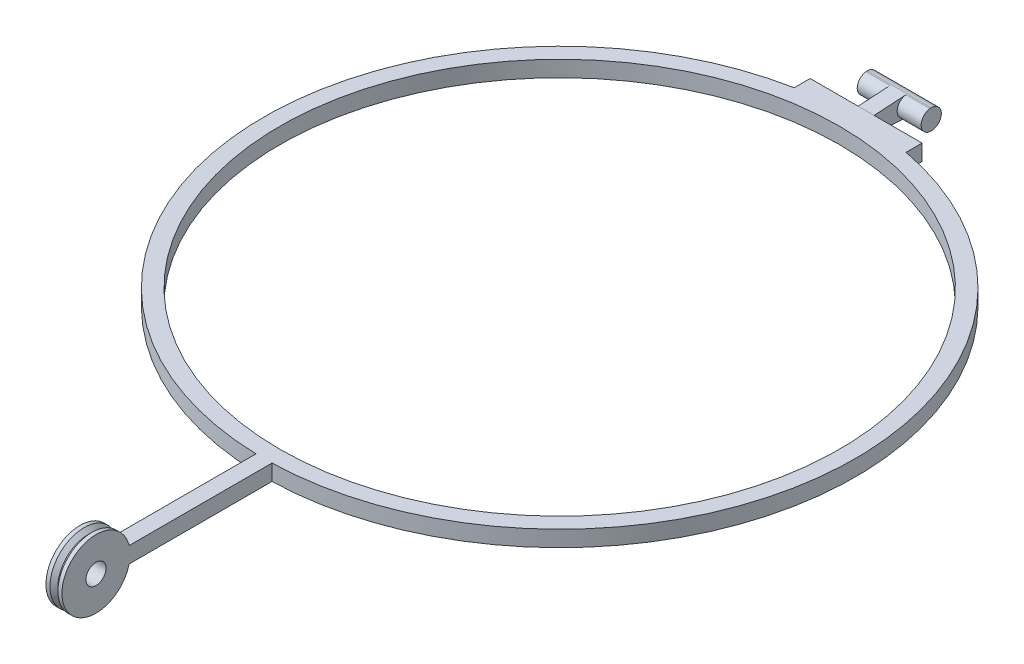
SolidWorks part; units mm, degrees
ref_plane "Front Plane" through (0, 0, 0) normal (0, 0, 1) x (1, 0, 0)
ref_plane "Top Plane" through (0, 0, 0) normal (0, 1, 0) x (1, 0, 0)
ref_plane "Right Plane" through (0, 0, 0) normal (1, 0, 0) x (0, 0, -1)
sketch "Sketch1" plane through (0, 0, 0) normal (0, 0, 1) x (1, 0, 0)
  line L0 (0, 0) -> (11.6505, 0) construction
  line L1 (0, 4) -> (6.35, 4)
  line L2 (0, 0) -> (0, 4) construction
  line L3 (0, 4) -> (0, 13.525)
  line L6 (6.35, 13.525) -> (6.35, 4)
  line L7 (3.175, 4) -> (3.175, 11.9375) construction
  line L8 (0, 13.525) -> (1.5875, 13.525)
  line L9 (1.5875, 13.525) -> (3.175, 11.9375)
  line L10 (4.7625, 13.525) -> (3.175, 11.9375)
  line L11 (6.35, 13.525) -> (4.7625, 13.525)
  dimension "D1" = 6.35
  dimension "D2" = 8
  dimension "D3" = 1.5875
  dimension "D4" = 9.525
  dimension "D5" = 1.5875
revolve "Revolve1" add sketch "Sketch1" angle 360 about L0
sketch "Sketch2" plane through (6.35, 0, 0) normal (1, 0, 0) x (0, 0, -1)
  line L0 (0, 0) -> (304.8, 0) construction
  line L1 (13.3018, 3.175) -> (304.8, 3.175)
  line L2 (304.8, 3.175) -> (304.8, 0)
  line L3 (13.3018, -3.175) -> (304.8, -3.175)
  line L4 (304.8, -3.175) -> (304.8, 0)
  circle A0 centre (0, 0) radius 4 construction
  circle A1 centre (0, 0) radius 4
  arc A7 (10.968, 4.7123) -> (10.968, -4.7123) centre (0, 0) ccw
  arc A8 (13.3018, -3.175) -> (10.968, -4.7123) centre (13.3018, -5.715) ccw
  arc A9 (13.3018, 3.175) -> (10.968, 4.7123) centre (13.3018, 5.715) cw
  circle A10 centre (0, 0) radius 11.9375 construction
  dimension "D3" = 2.54
  dimension "D1" = 304.8
  dimension "D2" = 6.35
extrude "Boss-Extrude1" add sketch "Sketch2" against normal up to surface (6.35 mm away) up to face at (0, 0, 4)
sketch "Sketch5" plane through (0, 3.175, 0) normal (0, 1, 0) x (1, 0, 0)
  line L0 (6.35, 304.8) -> (6.35, 13.3018) construction
  line L1 (0, 304.8) -> (6.35, 304.8)
  line L2 (0, 304.8) -> (0, 366.2512)
  line L3 (0, 366.2512) -> (6.35, 366.2512)
  line L4 (6.35, 304.8) -> (6.35, 366.2512)
extrude "Boss-Extrude3" [suppressed] add sketch "Sketch5" along normal blind 228.6
sketch "Sketch6" plane through (0, -3.175, 0) normal (0, -1, 0) x (1, 0, 0)
  line L0 (3.175, -298.45) -> (3.175, -43.3369) construction
  line L2 (0, -304.8) -> (0, -13.3018) construction
  line L3 (6.35, -13.3018) -> (6.35, -304.8) construction
  line L4 (-19.05, -302.6785) -> (-19.05, -309.0285)
  line L5 (-19.05, -309.0285) -> (25.4, -309.0285)
  line L6 (25.4, -309.0285) -> (25.4, -302.6785)
  line L7 (0, -304.8) -> (6.35, -304.8) construction
  circle A0 centre (3.175, -187.325) radius 111.125
  circle A1 centre (3.175, -187.325) radius 117.475
  point P0 (3.175, -295.9305)
  line M2 (0, -13.3018) -> (0, -304.8)
  line M3 (0, -304.8) -> (6.35, -304.8)
  line M4 (6.35, -304.8) -> (6.35, -13.3018)
  dimension "D4" = 222.25
  dimension "D2" = 6.35
  dimension "D3" = 44.45
  dimension "D1" = 6.35
extrude "Boss-Extrude4" add sketch "Sketch6" against normal blind 6.35 contours A1 A0 M2 | A1 A0 M4 | A1 L4 L5 L6 M4 M3 M2 region at (3.175, -3.175, -306.5222) region at (-111.3053, -3.175, -177.9565) region at (85.4857, -3.175, -107.2097)
extrude "Cut-Extrude1" cut sketch "Sketch6<4>" against normal through all both and the other way through all contours A0 L0 M2 | L0 A0 M4 region at (1.5876, -3.175, -187.325) region at (4.7624, -3.175, -187.325)
sketch "Sketch6<4>" plane through (0, -3.175, 0) normal (0, -1, 0) x (1, 0, 0) same geometry as "Sketch6"
ref_plane "Plane1" through (3.175, 0, 0) normal (-1, 0, 0) x (0, 0, 1)
sketch "Sketch8" plane through (3.175, 0, 0) normal (-1, 0, 0) x (0, 0, 1)
  line L0 (-302.6785, 0) -> (-322.191, 0) construction
  line L1 (-309.0285, 3.175) -> (-322.191, 4)
  line L2 (-309.0285, -3.175) -> (-322.191, -4)
  line L4 (-309.0285, -3.175) -> (-302.6785, -3.175)
  line L5 (-302.6785, -3.175) -> (-302.6785, 3.175)
  line L6 (-302.6785, 3.175) -> (-309.0285, 3.175)
  line L7 (-309.0285, 3.175) -> (-309.0285, -3.175)
  line L8 (-309.0285, -3.175) -> (-302.6785, -3.175)
  line L9 (-302.6785, -3.175) -> (-302.6785, 3.175)
  line L10 (-302.6785, 3.175) -> (-309.0285, 3.175)
  line L11 (-309.0285, 3.175) -> (-309.0285, -3.175)
  circle A0 centre (-322.191, 0) radius 11 construction
  circle A1 centre (-322.191, 0) radius 13.54 construction
  circle A2 centre (-322.191, 0) radius 4
  dimension "D2" = 22
  dimension "D4" = 8
  dimension "D1" = 0
  dimension "D3" = 2.54
extrude "Boss-Extrude5" add sketch "Sketch8" along normal mid plane 6.35 contours A2 L2 L11 L1 region at (3.175, 0, -314.1831)
extrude "Boss-Extrude6" add sketch "Sketch8<3>" along normal mid plane 25.4 contours L1 A2 L2 region at (3.175, 0, -322.191)
sketch "Sketch8<3>" plane through (3.175, 0, 0) normal (-1, 0, 0) x (0, 0, 1) same geometry as "Sketch8"
